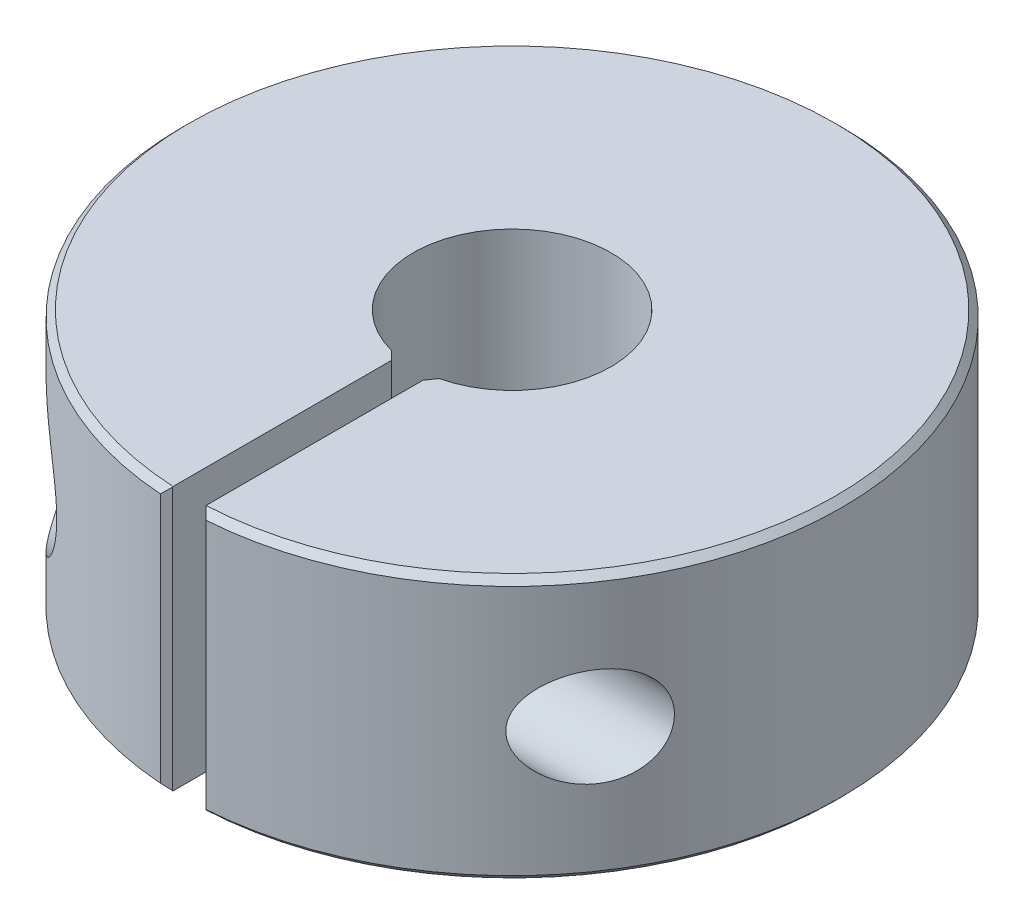
SolidWorks part; units mm, degrees
material "铸造合金钢"
ref_plane "前视基准面" through (0, 0, 0) normal (0, 0, 1) x (1, 0, 0)
ref_plane "上视基准面" through (0, 0, 0) normal (0, 1, 0) x (1, 0, 0)
ref_plane "右视基准面" through (0, 0, 0) normal (1, 0, 0) x (0, 0, -1)
sketch "草图1" plane through (0, 0, 0) normal (0, 1, 0) x (1, 0, 0)
  line L0 (0, -10) -> (0, 10) construction
  line L1 (-0.5, -2.958) -> (-0.5, -9.9875)
  line L2 (0.5, -2.958) -> (0.5, -9.9875)
  arc A0 (0.5, -2.958) -> (-0.5, -2.958) centre (0, 0) ccw
  arc A1 (0.5, -9.9875) -> (-0.5, -9.9875) centre (0, 0) ccw
  dimension "内径" = 6
  dimension "外径" = 20
  dimension "缝宽" = 1
extrude "凸台-拉伸1" add sketch "草图1" along normal mid plane 8
chamfer "倒角1" distance 0.2 angle 45 6 edges at (-0.5, 0, 9.9875) (0.5, 0, 9.9875) (0.5, 0, 2.958) (-0.5, 0, 2.958) (0, -4, -10) (0, 4, -10)
ref_plane "基准面1" through (-3, 0, 0) normal (1, 0, 0) x (0, 0, -1)
sketch "草图2" plane through (-3, 0, 0) normal (1, 0, 0) x (0, 0, -1)
  line L0 (-1000, 0) -> (49000, 0) construction
  line L1 (0, -1000) -> (0, 49000) construction
  line L2 (-2.9165, -4) -> (-2.9165, 4) construction
  circle A0 centre (-5.6665, 0) radius 2.75
  dimension "杯头外径" = 5.5
extrude "切除-拉伸1" cut sketch "草图2" against normal through all
sketch "草图3" plane through (-3, 0, 0) normal (1, 0, 0) x (0, 0, -1)
  circle A0 centre (-5.6665, 0) radius 1.5
  dimension "孔径" = 3
extrude "切除-拉伸2" cut sketch "草图3" along normal through all
other "冻结***"
